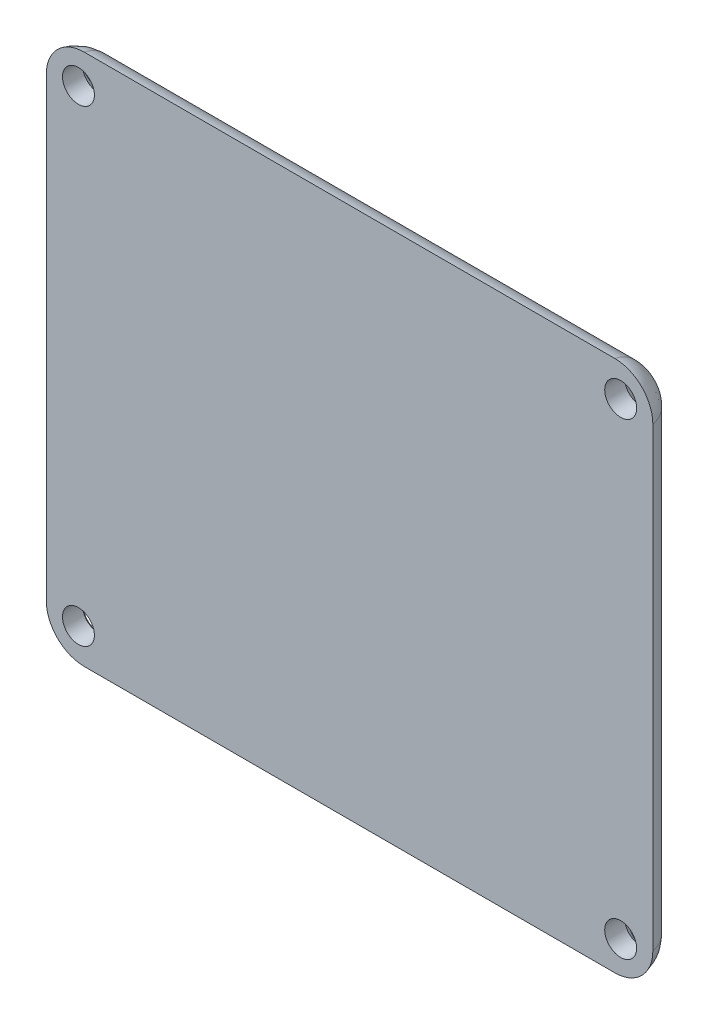
SolidWorks part; units mm, degrees
ref_plane "Ön Düzlem" through (0, 0, 0) normal (0, 0, 1) x (1, 0, 0)
ref_plane "Üst Düzlem" through (0, 0, 0) normal (0, 1, 0) x (1, 0, 0)
ref_plane "Sağ Düzlem" through (0, 0, 0) normal (1, 0, 0) x (0, 0, -1)
sketch "Çizim1" plane through (0, 0, 0) normal (0, 0, 1) x (1, 0, 0)
  line L1 (-39.9, -35) -> (39.9, -35)
  line L2 (-39.9, -35) -> (-39.9, 35)
  line L3 (-39.9, 35) -> (39.9, 35)
  line L4 (39.9, -35) -> (39.9, 35)
  line L5 (-39.9, -35) -> (39.9, 35) construction
  line L6 (-39.9, 35) -> (39.9, -35) construction
  point P0 (0, 0)
  dimension "D1" = 79.8
  dimension "D2" = 70
extrude "Yükseklik-Ekstrüzyon1" add sketch "Çizim1" along normal blind 4
fillet "Radyus1" radius 5 4 edges at (-39.9, -35, 2) (39.9, 35, 2) (39.9, -35, 2) (-39.9, 35, 2)
fillet "Radyus2" radius 5 8 edges at (38.4355, -33.5355, 0) (0, -35, 0) (-38.4355, -33.5355, 0) (-39.9, 0, 0) (-38.4355, 33.5355, 0) (0, 35, 0) (38.4355, 33.5355, 0) (39.9, 0, 0)
sketch "Çizim3" plane through (0, 0, 0) normal (0, 0, -1) x (-1, 0, 0)
  point P0 (35.6678, -30.7678)
  point P1 (-35.6678, -30.7678)
  point P3 (-35.6678, 30.7678)
  point P5 (35.6678, 30.7678)
hole_wizard "Delik1" positions "Çizim4" profile "Çizim5" legacy
sketch "Çizim4" plane through (0, 0, 0) normal (0, 0, -1) x (-1, 0, 0)
  point P0 (-35.6678, 30.7678)
  point P3 (35.6678, 30.7678)
  point P6 (35.6678, -30.7678)
  point P9 (-35.6678, -30.7678)
sketch "Çizim5" plane through (35.6678, 30.7678, 0) normal (1, 0, 0) x (0, 1, 0)
  line L0 (0, 0) -> (0, 5)
  line L1 (0, 5) -> (2.1, 5)
  line L2 (2.1, 5) -> (2.1, 1.3705)
  line L3 (2.1, 1.3705) -> (3.25, 0)
  line L4 (3.25, 0) -> (0, 0)
  line L5 (0, -6.4453) -> (0, 115.525) construction
  line L6 (-2.1, 1.3705) -> (-3.25, 0) construction
  dimension "Diameter" = 4.2
  dimension "Depth" = 5
  dimension "C-Sink Angle" = 80
  dimension "C-Sink Diameter" = 6.5
